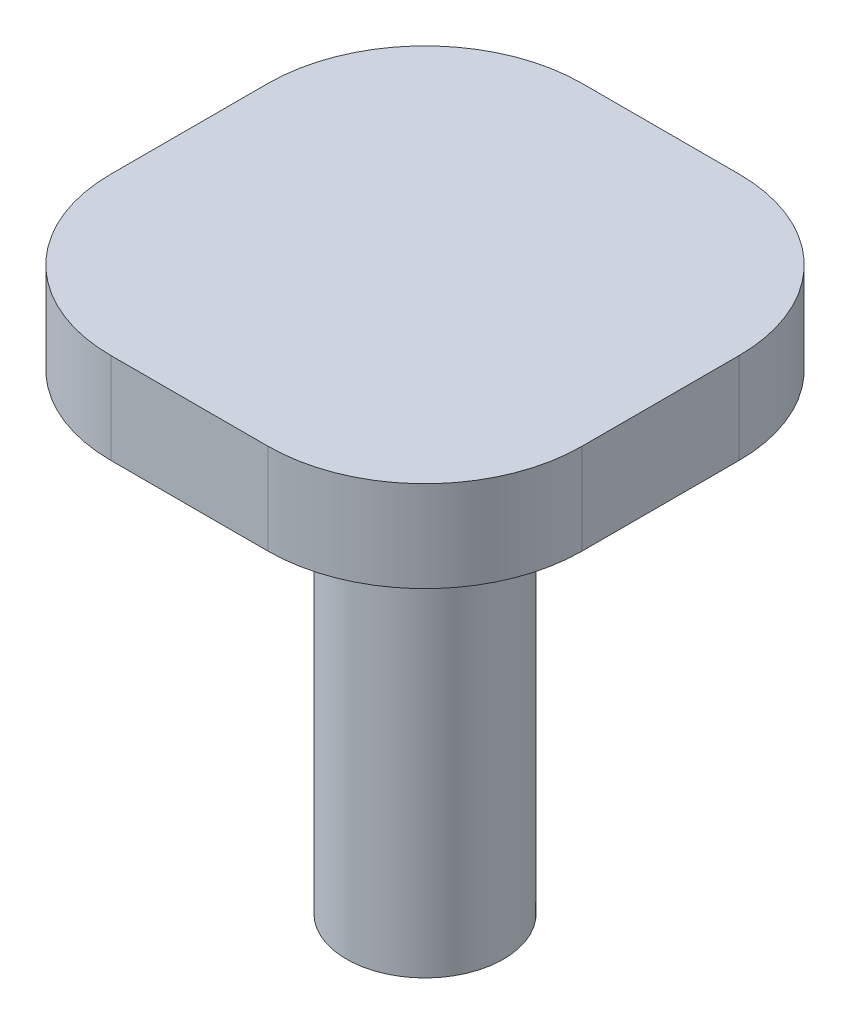
SolidWorks part; units mm, degrees
ref_plane "Front Plane" through (0, 0, 0) normal (0, 0, 1) x (1, 0, 0)
ref_plane "Top Plane" through (0, 0, 0) normal (0, 1, 0) x (1, 0, 0)
ref_plane "Right Plane" through (0, 0, 0) normal (1, 0, 0) x (0, 0, -1)
sketch "Sketch1" plane through (0, 0, 0) normal (0, 0, 1) x (1, 0, 0)
  line L0 (-0.5, 3) -> (0.5, 3)
  line L1 (0.5, -3) -> (-0.5, -3)
  line L2 (0.5, -3) -> (0.5, 3)
  line L4 (-0.5, -3) -> (-0.5, 3)
  line L5 (0.5, -3) -> (-0.5, 3) construction
  line L6 (0.5, 3) -> (-0.5, -3) construction
  line L7 (0, -998.2005) -> (0, 49001.7995) construction
  point P0 (0, 0)
  dimension "D1" = 6
  dimension "D2" = 1
revolve "Revolve3" add sketch "Sketch1" angle 360 about L4
sketch "Sketch9" plane through (0, 0, 0) normal (0, 0, 1) x (1, 0, 0)
  line L0 (0.5, -3) -> (0.5, 3) construction
  line L1 (-0.5, 3) -> (-0.5, -3) construction
  line L2 (0.5, 3) -> (-1.5, 3) construction
  line L3 (-1.5, -3) -> (0.5, -3) construction
  line L4 (-1.5, 3) -> (-1.5, -3) construction
  line L5 (2.5, 3) -> (-3.5, 3)
  line L6 (2.5, 3) -> (2.5, 4.157)
  line L7 (2.5, 4.157) -> (-3.5, 4.157)
  line L8 (-3.5, 3) -> (-3.5, 4.157)
  line L9 (2.5, 3) -> (-3.5, 4.157) construction
  line L10 (2.5, 4.157) -> (-3.5, 3) construction
  point P0 (-0.5, 3.5785)
  dimension "D1" = 0
  dimension "D2" = 2
  dimension "D3" = 2
extrude "Boss-Extrude1" add sketch "Sketch9" along normal blind 3 and the other way blind 3
fillet "Fillet1" radius 2 4 edges at (-3.5, 3.5785, -3) (2.5, 3.5785, -3) (2.5, 3.5785, 3) (-3.5, 3.5785, 3)
